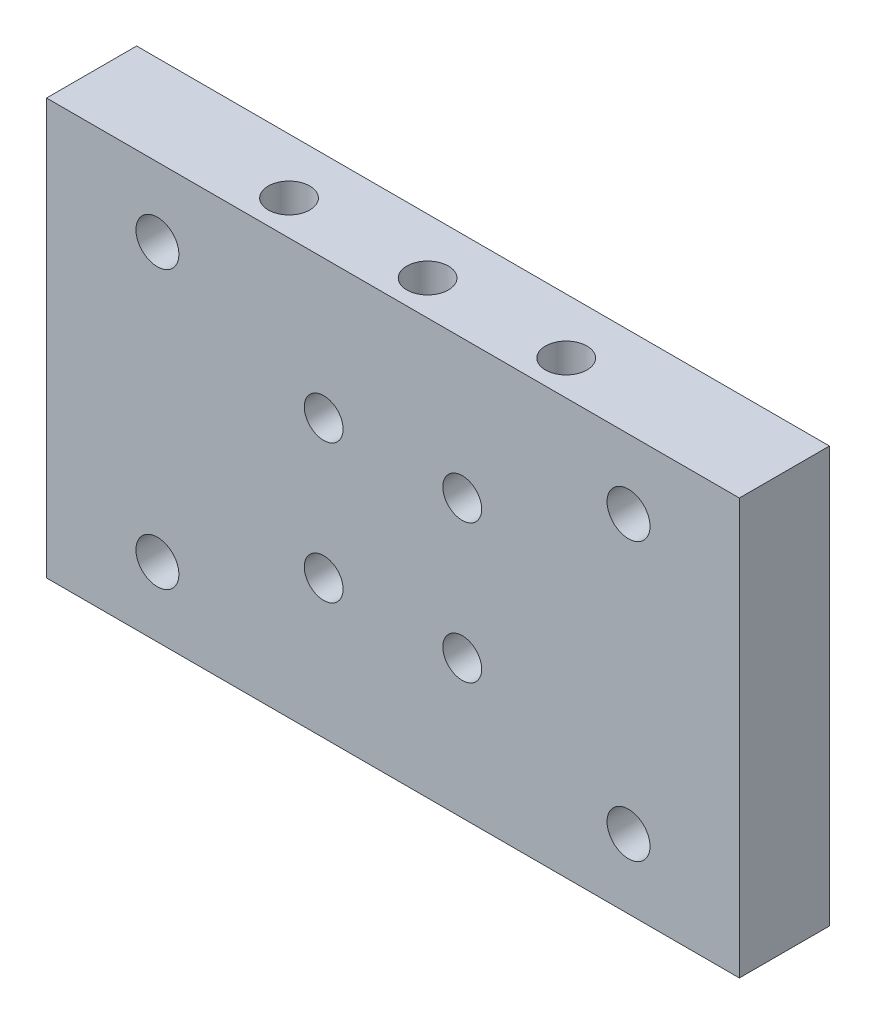
SolidWorks part; units mm, degrees
ref_plane "前视基准面" through (0, 0, 0) normal (0, 0, 1) x (1, 0, 0)
ref_plane "上视基准面" through (0, 0, 0) normal (0, 1, 0) x (1, 0, 0)
ref_plane "右视基准面" through (0, 0, 0) normal (1, 0, 0) x (0, 0, -1)
sketch "草图1" plane through (0, 0, 0) normal (0, 0, 1) x (1, 0, 0)
  line L1 (25, -15) -> (-25, -15)
  line L2 (25, -15) -> (25, 15)
  line L3 (25, 15) -> (-25, 15)
  line L4 (-25, -15) -> (-25, 15)
  line L5 (25, -15) -> (-25, 15) construction
  line L6 (25, 15) -> (-25, -15) construction
  point P0 (0, 0)
  dimension "D1" = 30
  dimension "D2" = 50
extrude "凸台-拉伸1" add sketch "草图1" along normal blind 6.5
sketch "草图2" plane through (0, 0, 6.5) normal (0, 0, 1) x (1, 0, 0)
  line L1 (5, -5) -> (-5, -5)
  line L2 (5, -5) -> (5, 5)
  line L3 (5, 5) -> (-5, 5)
  line L4 (-5, -5) -> (-5, 5)
  line L5 (5, -5) -> (-5, 5) construction
  line L6 (5, 5) -> (-5, -5) construction
  circle A0 centre (5, 5) radius 1.4
  circle A1 centre (-5, 5) radius 1.4
  circle A2 centre (-5, -5) radius 1.4
  circle A3 centre (5, -5) radius 1.4
  point P0 (0, 0)
  dimension "D1" = 10
  dimension "D3" = 2.8
  dimension "D2" = 10
extrude "切除-拉伸1" cut sketch "草图2" against normal through all contours L3 A1 L4 | L4 A1 L3 | L3 A0 L2 | L2 A0 L3 | L1 A3 L2 | L2 A3 L1 | L4 A2 L1 | L1 A2 L4 region at (-5.1981, -5.1981, 6.5) region at (-4.4058, -4.4058, 6.5) region at (4.4058, -4.4058, 6.5) region at (5.1981, -5.1981, 6.5) region at (-5.1981, 5.1981, 6.5) region at (-4.4058, 4.4058, 6.5) region at (4.4058, 4.4058, 6.5) region at (5.1981, 5.1981, 6.5)
sketch "草图4" plane through (0, 0, 0) normal (0, 0, -1) x (-1, 0, 0)
  line L0 (-25, 0) -> (-17, 0) construction
  line L1 (-25, -15) -> (-25, 15) construction
  line L2 (-17, 0) -> (-17, 10) construction
  line L3 (0, 0) -> (0, -15) construction
  line L4 (25, -15) -> (-25, -15) construction
  line L5 (17, 0) -> (17, 10) construction
  circle A0 centre (-17, 10) radius 1.55
  circle A1 centre (-17, -10) radius 1.55
  circle A2 centre (17, -10) radius 1.55
  circle A3 centre (17, 10) radius 1.55
  dimension "D1" = 3.1
  dimension "D2" = 10
  dimension "D3" = 8
extrude "切除-拉伸2" cut sketch "草图4" against normal through all
sketch "草图5" plane through (0, 15, 0) normal (0, 1, 0) x (1, 0, 0)
  circle A0 centre (-10, -4) radius 1.5
  circle A1 centre (0, -4) radius 1.5
  circle A2 centre (10, -4) radius 1.5
extrude "切除-拉伸3" cut sketch "草图5" against normal through all
